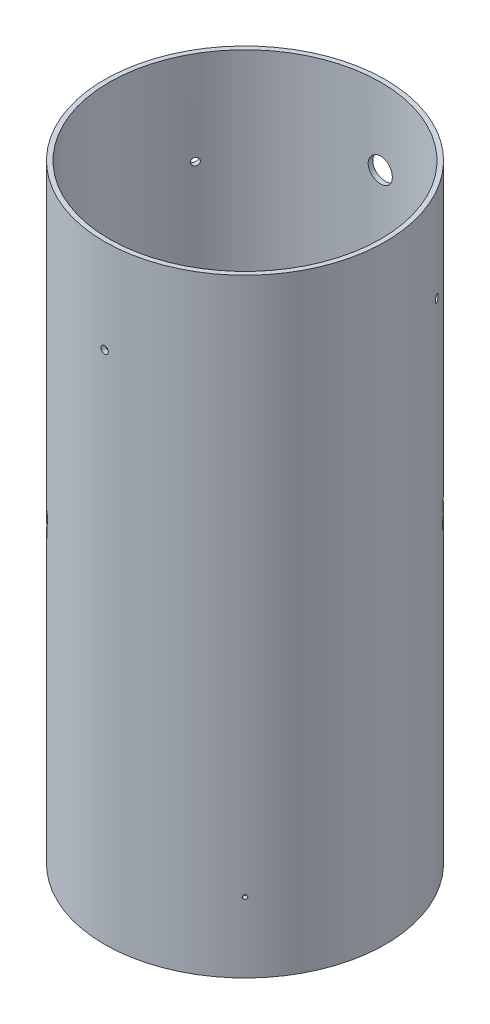
SolidWorks part; units mm, degrees
material "A-Glass Fiber"
ref_plane "Front Plane" through (0, 0, 0) normal (0, 0, 1) x (1, 0, 0)
ref_plane "Top Plane" through (0, 0, 0) normal (0, 1, 0) x (1, 0, 0)
ref_plane "Right Plane" through (0, 0, 0) normal (1, 0, 0) x (0, 0, -1)
sketch "Sketch1" plane through (0, 0, 0) normal (0, 1, 0) x (1, 0, 0)
  circle A0 centre (0, 0) radius 76.1746
  circle A1 centre (0, 0) radius 73.66
  dimension "D1" = 152.3492
  dimension "D2" = 147.32
extrude "Boss-Extrude1" add sketch "Sketch1" along normal blind 330.2
sketch "Sketch4" plane through (0, 0, 0) normal (0, 0, 1) x (1, 0, 0)
  line L0 (-76.1746, 0) -> (76.1746, 0) construction
  line L1 (76.1746, 330.2) -> (-76.1746, 330.2) construction
  line L2 (0, 330.2) -> (0, 0) construction
  line L3 (73.66, 330.2) -> (-73.66, 330.2) construction
  point P0 (0, 41.275)
  point P3 (0, 288.925)
  dimension "D1" = 41.275
  dimension "D2" = 41.275
hole_wizard "1/2 Clearance Hole5" positions "Sketch16" profile "Sketch17" hole size "1/2" standard "ANSI Inch"
sketch "Sketch16" plane through (0, 0, 0) normal (0, 0, 1) x (1, 0, 0)
  point P0 (0, 288.925)
sketch "Sketch17" plane through (0, 288.925, 0) normal (1, 0, 0) x (0, -1, 0)
  line L0 (0, 0) -> (0, 80.1345)
  line L1 (0, 80.1345) -> (6.5481, 76.2)
  line L2 (6.5481, 76.2) -> (6.5481, 0)
  line L5 (6.5481, 0) -> (0, 0)
  line L10 (0, 80.1345) -> (-6.5481, 76.2) construction
  line L11 (0, -6.35) -> (0, 107.95) construction
  dimension "Hole Dia." = 13.0962
  dimension "Hole Depth" = 76.2
  dimension "Drill Angle" = 118
hole_wizard "1/2 Clearance Hole7" positions "Sketch20" profile "Sketch21" hole size "1/2" standard "ANSI Inch"
sketch "Sketch20" plane through (0, 0, 0) normal (0, 0, 1) x (1, 0, 0)
  point P0 (0, 41.275)
sketch "Sketch21" plane through (0, 41.275, 0) normal (1, 0, 0) x (0, -1, 0)
  line L0 (0, 0) -> (0, 80.1345)
  line L1 (0, 80.1345) -> (6.5481, 76.2)
  line L2 (6.5481, 76.2) -> (6.5481, 0)
  line L5 (6.5481, 0) -> (0, 0)
  line L10 (0, 80.1345) -> (-6.5481, 76.2) construction
  line L11 (0, -6.35) -> (0, 107.95) construction
  dimension "Hole Dia." = 13.0962
  dimension "Hole Depth" = 76.2
  dimension "Drill Angle" = 118
ref_plane "Plane1" through (0, 0, 0) normal (-0.7071, 0, 0.7071) x (0.7071, 0, 0.7071)
sketch "Sketch23" plane through (0, 0, 0) normal (-0.7071, 0, 0.7071) x (0.7071, 0, 0.7071)
  line L0 (0, 0) -> (0, 330.2) construction
  line L1 (73.66, 330.2) -> (-73.66, 330.2) construction
  line L2 (-76.1746, 165.1) -> (76.1746, 165.1) construction
  line L3 (76.1746, 0) -> (76.1746, 330.2) construction
  circle A1 centre (0, 38.1) radius 1.0922
  point P12 (0, 165.1)
  dimension "D2" = 127
extrude "Shear Scrrews" cut sketch "Sketch23" against normal through all
pattern_circular "CirPattern1" count 4 over 360 about axis through (0, 330.2, 0) along (0, -1, 0) of "Shear Scrrews"
hole_wizard "Ø4.0 (4) Diameter Hole1" positions "Sketch24" profile "Sketch25" hole size "Ø4.0" standard "ANSI Metric"
sketch "Sketch24" plane through (0, 0, 0) normal (0, 0, 1) x (1, 0, 0)
  line L0 (76.1746, 330.2) -> (-76.1746, 330.2) construction
  point P0 (0, 279.4)
  dimension "D1" = 50.8
sketch "Sketch25" plane through (0, 279.4, 0) normal (1, 0, 0) x (0, 1, 0)
  line L0 (0, 0) -> (0, 90.1017)
  line L1 (0, 90.1017) -> (2, 88.9)
  line L2 (2, 88.9) -> (2, 0)
  line L5 (2, 0) -> (0, 0)
  line L10 (0, 90.1017) -> (-2, 88.9) construction
  line L11 (0, -6.35) -> (0, 107.95) construction
  dimension "Hole Dia." = 4
  dimension "Hole Depth" = 88.9
  dimension "Drill Angle" = 118
pattern_circular "CirPattern2" count 3 over 360 about axis through (0, 330.2, 0) along (0, 1, 0) of "Ø4.0 (4) Diameter Hole1"
ref_plane "Camera Cutout Plane" through (0, 0, 0) normal (0.7071, 0, -0.7071) x (0, -1, 0)
sketch "Sketch26" plane through (0, 0, 0) normal (0.7071, 0, -0.7071) x (0, -1, 0)
  line L0 (-330.2, 0) -> (0, 0) construction
  line L1 (-174.625, -5) -> (-167.625, -5)
  line L2 (-174.625, -5) -> (-174.625, 5)
  line L3 (-174.625, 5) -> (-167.625, 5)
  line L4 (-167.625, -5) -> (-167.625, 5)
  line L5 (-174.625, -5) -> (-167.625, 5) construction
  line L6 (-174.625, 5) -> (-167.625, -5) construction
  line L7 (-330.2, 76.1746) -> (-330.2, -76.1746) construction
  circle A0 centre (-158.735, 0) radius 2.75
  point P0 (-171.125, 0)
  dimension "D4" = 5.5
  dimension "D1" = 7
  dimension "D2" = 10
  dimension "D3" = 155.575
  dimension "D5" = 8.89
extrude "Upwards Camera Cutout" cut sketch "Sketch26" along normal through all
sketch "Sketch27" plane through (0, 0, 0) normal (0.7071, 0, -0.7071) x (0, -1, 0)
  line L0 (-330.2, 0) -> (0, 0) construction
  line L1 (-155.575, 5) -> (-162.575, 5)
  line L2 (-155.575, 5) -> (-155.575, -5)
  line L3 (-155.575, -5) -> (-162.575, -5)
  line L4 (-162.575, 5) -> (-162.575, -5)
  line L5 (-155.575, 5) -> (-162.575, -5) construction
  line L6 (-155.575, -5) -> (-162.575, 5) construction
  line L8 (0, -76.1746) -> (0, 76.1746) construction
  circle A0 centre (-171.465, 0) radius 2.75
  point P0 (-159.075, 0)
  dimension "D4" = 5.5
  dimension "D1" = 7
  dimension "D2" = 10
  dimension "D3" = 8.89
  dimension "D5" = 155.575
extrude "Downwards Camera Cutout" cut sketch "Sketch27" against normal through all
ref_plane "Camera Side Hole Plane" through (0, 0, 0) normal (0.7567, 0, -0.6537) x (0, -1, 0)
sketch "Sketch28" plane through (0, 0, 0) normal (0.7567, 0, -0.6537) x (0, -1, 0)
  line L0 (-330.2, 0) -> (0, 0) construction
  line L1 (-162.575, -10.5216) -> (-162.575, -0.5482) construction
  circle A0 centre (-166.385, 0) radius 2.75
  dimension "D1" = 5.5
  dimension "D2" = 3.81
extrude "Cut-Extrude4" cut sketch "Sketch28" against normal through all
pattern_circular "CirPattern3" count 2 every 8.407 about axis through (0, 0, 0) along (0, 1, 0) of "Cut-Extrude4"
sketch "Sketch29" plane through (0, 0, 0) normal (0.7567, 0, -0.6537) x (0, -1, 0)
  line L0 (-330.2, 0) -> (0, 0) construction
  line L1 (-167.625, 10.3381) -> (-167.625, 0.3647) construction
  circle A0 centre (-163.815, 0) radius 2.75
  dimension "D1" = 5.5
  dimension "D2" = 3.81
extrude "Cut-Extrude5" cut sketch "Sketch29" along normal through all
pattern_circular "CirPattern4" count 2 every 8.407 about axis through (0, 330.2, 0) along (0, 1, 0) of "Cut-Extrude5"
equation "\"Mid_Coupler_Length\"= 13in"
equation "\"D1@Boss-Extrude1\"=\"Mid_Coupler_Length\""
equation "\"Shear_Screw_Coupler_Location\"= 4.5in"
equation "\"Shear_Screw_Diameter\"= 0.086in"
equation "\"D2@Sketch23\"=\"Shear_Screw_Coupler_Location\"+0.5"
equation "\"Mid_Tube_Length\"= 1in"
equation "\"Bodytube_OD\"= 6.17in"
equation "\"Bodytube_ID\"= 5.998in"
equation "\"Camera_Cutout_Width\"=10mm"
equation "\"Camera_Cutout_Height\"=7mm"
equation "\"Fwd_Tube_Length\"= 40in"
equation "\"BKHD_Screw_Diam\"= 3.5mm"
equation "\"Fwd_BKHD_From_Top\"= 18in"
equation "\"Motor_OD\"= 4in"
equation "\"Aft_Section_Length\"= 39in"
equation "\"AB_Coupler_OD_Length\"= 1in"
equation "\"AB_Coupling_Section_Length\"= 0.375in"
equation "\"AB_Coupler_Length\"= \"AB_Coupler_OD_Length\" + \"AB_Coupling_Section_Length\" * 2"
equation "\"Cutout_Angle\"= 80"
equation "\"AB_Paddle_Height\"= 0.375in"
equation "\"AB_Coupler_Num_Screws\"= 4"
equation "\"AB_BKHD_Thickness\"= 0.375in"
equation "\"AB_Mount_From_Bottom\"= 23.175in"
equation "\"Num_Cutouts\"= 3"
equation "\"AB_Coupler_OD\"= 6.17in"
equation "\"AB_Coupler_ID\"= 5.75in"
equation "\"AB_Coupler_Surface_Diameter\"= 5.998in"
equation "\"AB_Coupling_Screw_Diameter\"= 0.15748in"
equation "\"AB_Central_Bushing_Length\"= .4724in"
equation "\"Lead_Screw_Dist\"= 3.4in"
equation "\"Lead_Screw_Diam\"= 0.386in"
equation "\"Lead_Screw_Length\"= (\"Mid_Coupler_Length\" + 2*0.375in + 2*0.5in)"
equation "\"Paddle_Pin_Offset\"= .25in"
equation "\"Paddle_Pin_Radius\"= 2.25in"
equation "\"SS_Paddle_Pin_Radius\"= 2.25*0.66in"
equation "\"Paddle_Gear_OD\"= 3.2in"
equation "\"Drive_Gear_OD\"= 1.7in"
equation "\"Fin_Thickness\"= .118in"
equation "\"Guiderail_Cutout_Diameter\"= 1.5in"
equation "\"DB9_Hole_Dist\"= 25mm"
equation "\"DB9_Relief_Width\"= 0.47in"
equation "\"DB9_Relief_Hole_Offset\"= 0.09in"
equation "\"Airbrakes_Wire_Hole_Dia\"= .25in"
equation "\"Airbrakes_Wire_Hole_Dist\"= 1.1in"
equation "\"Servo_Gear_Offset\"= 0.5in"
equation "\"FWD_Shear_Screw_Dist\"= 1.5in"
equation "\"Camera_Screw_Dia\"= 0.216535"
equation "\"Camera_Hole_Angle\"= atn ( 2 / 3 * tan ( 12.5deg ) )"
equation "\"D1@Sketch26\"=\"Camera_Cutout_Height\""
equation "\"D2@Sketch26\"=\"Camera_Cutout_Width\""
equation "\"D3@Sketch26\"=6.125"
equation "\"D1@Sketch27\"=\"Camera_Cutout_Height\""
equation "\"D2@Sketch27\"=\"Camera_Cutout_Width\""
equation "\"D1@Sketch28\"=\"Camera_Screw_Dia\""
equation "\"D2@CirPattern3\"=\"Camera_Hole_Angle\""
equation "\"D1@Sketch29\"=\"Camera_Screw_Dia\""
equation "\"D2@CirPattern4\"=\"Camera_Hole_Angle\""
equation "\"Coupler_OD\"= 5.998"
equation "\"D1@Sketch1\"=\"Coupler_OD\""
equation "\"Coupler_ID\"= 5.8"
equation "\"D2@Sketch1\"=\"Coupler_ID\""
